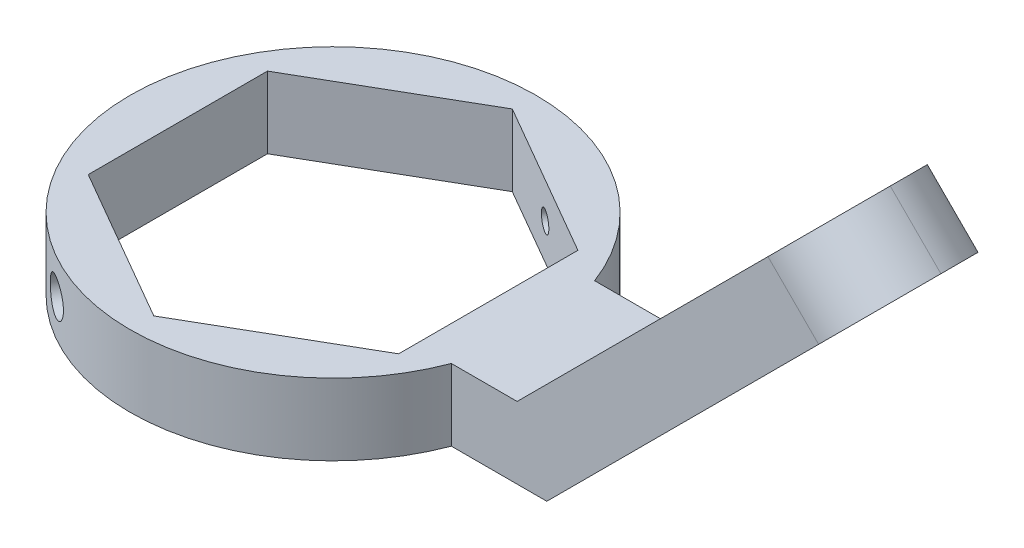
SolidWorks part; units mm, degrees
ref_plane "Front Plane" through (0, 0, 0) normal (0, 0, 1) x (1, 0, 0)
ref_plane "Top Plane" through (0, 0, 0) normal (0, 1, 0) x (1, 0, 0)
ref_plane "Right Plane" through (0, 0, 0) normal (1, 0, 0) x (0, 0, -1)
sketch "Sketch2" plane through (0, 0, 0) normal (0, 0, 1) x (1, 0, 0)
  line L0 (0, 0) -> (47.8, 0) construction
  line L1 (47.8, 0) -> (90.5, 42.7) construction
  dimension "D1" = 42.7
  dimension "D2" = 90.5
  dimension "D3" = 45
sketch "Sketch3" plane through (0, 0, 0) normal (0, 1, 0) x (1, 0, 0)
  line L1 (0, 30.0222) -> (-26, 15.0111)
  line L2 (-26, 15.0111) -> (-26, -15.0111)
  line L3 (-26, -15.0111) -> (0, -30.0222)
  line L4 (0, -30.0222) -> (26, -15.0111)
  line L5 (26, -15.0111) -> (26, 15.0111)
  line L6 (26, 15.0111) -> (0, 30.0222)
  line L7 (20.2, -12) -> (47.8, -12)
  line L8 (20.2, -12) -> (20.2, 12)
  line L9 (20.2, 12) -> (47.8, 12)
  line L10 (47.8, -12) -> (47.8, 12)
  line L11 (20.2, -12) -> (47.8, 12) construction
  line L12 (20.2, 12) -> (47.8, -12) construction
  circle A0 centre (0, 0) radius 26 construction
  circle A1 centre (0, 0) radius 34
  point P10 (34, 0)
  point P18 (47.8, 0)
  dimension "D1" = 52
  dimension "D2" = 68
  dimension "D3" = 24
extrude "Boss-Extrude1" add sketch "Sketch3" along normal blind 12 contours L9 A1 L7 L5 L4 L3 L2 L1 L6 | L7 A1 L9 L5 | A1 L7 L10 L9 region at (-13.4732, 0, -23.3362) region at (29.6691, 0, 0) region at (40.5256, 0, 0)
ref_plane "Plane1" through (23.9, -23.9, 0) normal (0.7071, -0.7071, 0) x (0.7071, 0.7071, 0)
sketch "Sketch4" plane through (23.9, -23.9, 0) normal (0.7071, -0.7071, 0) x (0.7071, 0.7071, 0)
  line L0 (33.7997, 0) -> (94.1866, 0) construction
  line L2 (33.7997, 12) -> (110.1866, 12)
  line L3 (33.7997, 12) -> (33.7997, -12)
  line L4 (33.7997, -12) -> (110.1866, -12)
  line L5 (110.1866, 12) -> (110.1866, -12)
  circle A0 centre (94.1866, 0) radius 8
  circle A1 centre (94.1866, 0) radius 4
  dimension "D1" = 16
  dimension "D2" = 8
  dimension "D3" = 24
  dimension "D4" = 16
extrude "Boss-Extrude2" add sketch "Sketch4" against normal blind 12 contours A1 | L2 L5 L4 L3 region at (90.5, 42.7, 0)
extrude "Cut-Extrude1" cut sketch "Sketch4<3>" against normal blind 5.15 contours A0 | A1
sketch "Sketch4<3>" plane through (23.9, -23.9, 0) normal (0.7071, -0.7071, 0) x (0.7071, 0.7071, 0) same geometry as "Sketch4"
fillet "Fillet1" radius 12 2 edges at (97.5711, 58.2563, -12) (97.5711, 58.2563, 12)
sketch "Sketch5" plane through (13, 0, -22.5167) normal (-0.5, 0, 0.866) x (0.866, 0, 0.5)
  line L0 (15.0111, 12) -> (15.0111, 0) construction
  line L1 (15.0111, 12) -> (-15.0111, 12) construction
  circle A0 centre (0, 6) radius 1.7
  circle A1 centre (0, 6) radius 3
  point P5 (15.0111, 6)
  point P8 (0, 12)
  dimension "D1" = 6
  dimension "D2" = 3.4
extrude "Cut-Extrude2" cut sketch "Sketch5" against normal through all contours A0 region at (13, 6, -22.5167)
extrude "Cut-Extrude3" cut sketch "Sketch5<3>" against normal through all from offset 5 contours A1 offset against normal yes
sketch "Sketch5<3>" plane through (13, 0, -22.5167) normal (-0.5, 0, 0.866) x (0.866, 0, 0.5) same geometry as "Sketch5"
ref_plane "Plane2" through (0, 0, 0) normal (-0.5, 0, 0.866) x (0.866, 0, 0.5)
mirror "Mirror1" about plane through (0, 0, 0) normal (-0.5, 0, 0.866) of "Cut-Extrude3", "Cut-Extrude2"
equation "\"hexD\"=52"
equation "\"D1@Sketch3\"=\"hexD\""
equation "\"D\"=68"
equation "\"D2@Sketch3\"=\"D\""
